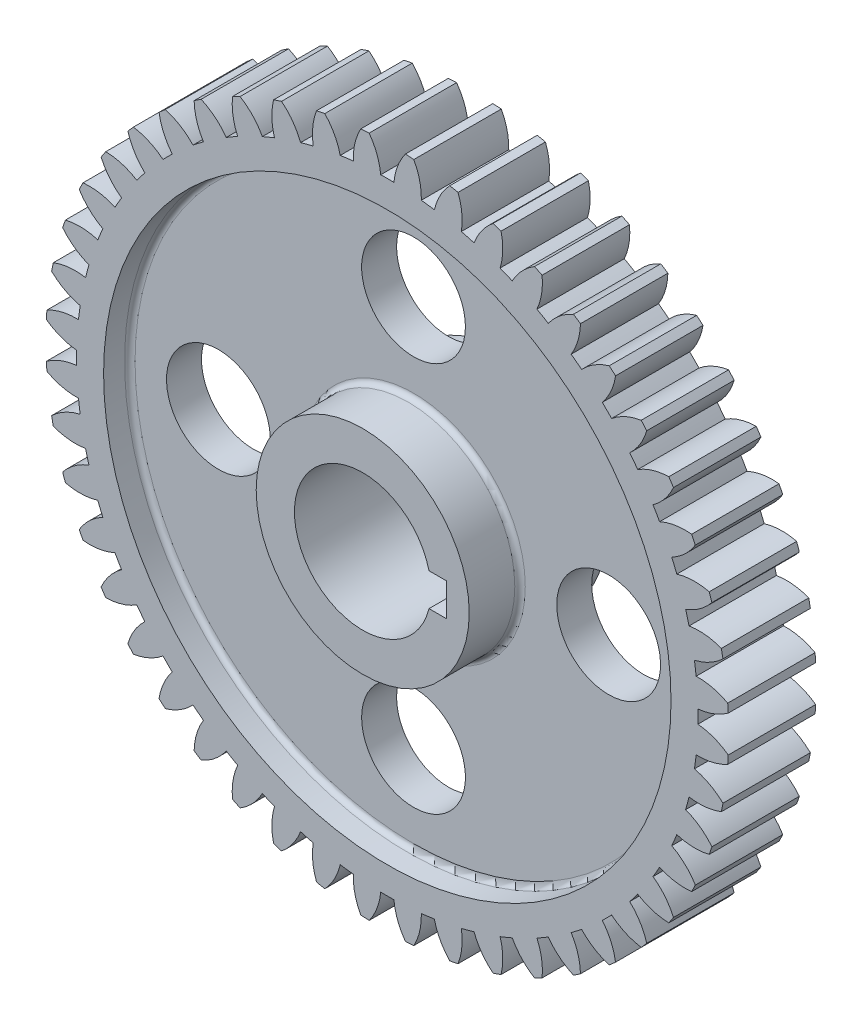
SolidWorks part; units mm, degrees
ref_plane "Front Plane" through (0, 0, 0) normal (0, 0, 1) x (1, 0, 0)
ref_plane "Top Plane" through (0, 0, 0) normal (0, 1, 0) x (1, 0, 0)
ref_plane "Right Plane" through (0, 0, 0) normal (1, 0, 0) x (0, 0, -1)
sketch "HoldingSke" plane through (0, 0, 0) normal (0, 0, 1) x (1, 0, 0)
  line L0 (0, 0) -> (0, -48) construction
  line L1 (0, 0) -> (2.5, 0) construction
  line L2 (0, 0) -> (48, 0) construction
sketch "BasProSke" plane through (0, 0, 0) normal (1, 0, 0) x (0, 0, -1)
  line L0 (-53.9382, 0) -> (60.1411, 0) construction
  line L1 (0, 64.4562) -> (0, -59.6017) construction
  line L3 (-8, 62.5) -> (8, 62.5)
  line L4 (-8, 62.5) -> (-8, 0)
  line L5 (-8, 0) -> (8, 0)
  line L6 (8, 62.5) -> (8, 0)
revolve "Base-Revolve" add sketch "BasProSke" angle 360 about L0
sketch "ToothCutSke" plane through (0, 0, 0) normal (0, 0, 1) x (1, 0, 0)
  line L0 (0, 0) -> (0, 94.1456) construction
  line L1 (0, 0) -> (-5.9046, 90.0862) construction
  line L2 (0, 0) -> (-2.3315, 71.2185) construction
  line L3 (-1.0192, 57.6168) -> (-2.6775, 61.7472) construction
  circle A0 centre (0, 0) radius 56.875 construction
  circle A1 centre (0, 0) radius 62.5 construction
  circle A2 centre (0, 0) radius 60 construction
  arc A3 (-1.2057, 56.8622) -> (-3.3184, 62.4118) centre (-12.4031, 55.7763) ccw
  arc A4 (3.3184, 62.4118) -> (1.2057, 56.8622) centre (12.4031, 55.7763) ccw
  circle A5 centre (0, 0) radius 62.5 construction
  circle A6 centre (0, 0) radius 57.1387 construction
  arc A7 (-3.3184, 62.4118) -> (3.3184, 62.4118) centre (0, 0) cw
  arc A8 (-1.2057, 56.8622) -> (1.2057, 56.8622) centre (0, 0) cw
  point P8 (-1.9631, 59.9679)
  dimension "D4" = 11.25
  dimension "D3" = 1.875
  dimension "D1" = 20
extrude "ToothCut" cut sketch "ToothCutSke" against normal mid plane 16
pattern_circular "TeethCuts" count 49 every 7.5 about axis through (0, 0, 53.9382) along (0, 0, -1) of "ToothCut"
sketch "BSke" plane through (0, 0, 0) normal (0, 0, 1) x (1, 0, 0)
  circle A0 centre (0, 0) radius 19.5
  circle A1 centre (0, 0) radius 12.5 construction
  dimension "Bore_diameter" = 25
extrude "B" [suppressed] add sketch "BSke" along normal blind 25 from surface starting at face at (0, 0, -8)
sketch "CSke" plane through (0, 0, 0) normal (0, 0, 1) x (1, 0, 0)
  circle A0 centre (0, 0) radius 19.5
  circle A1 centre (0, 0) radius 19.5 construction
extrude "C" add sketch "CSke" along normal mid plane 25
sketch "BoreSke" plane through (0, 0, 0) normal (0, 0, 1) x (1, 0, 0)
  circle A0 centre (0, 0) radius 12.5
  dimension "Bore_diameter" = 25
extrude "Bore" cut sketch "BoreSke" against normal mid plane 80
sketch "KeySke" plane through (0, 0, 0) normal (0, 0, 1) x (1, 0, 0)
  line L0 (0, 0) -> (50.2431, 0) construction
  line L1 (15.3, 3) -> (0, 3)
  line L2 (15.3, 3) -> (15.3, -3)
  line L3 (15.3, -3) -> (0, -3)
  line L4 (0, 3) -> (0, -3)
  line L5 (12.5, 26.1066) -> (12.5, -22.6354) construction
  circle A1 centre (0, 0) radius 12.5 construction
  dimension "Keyslot_width" = 6
  dimension "Keyslot_height" = 2.8
extrude "Keyway" cut sketch "KeySke" against normal mid plane 80
sketch "Cut1Ske" plane through (0, 0, 0) normal (1, 0, 0) x (0, 0, -1)
  line L1 (-67.2, 51.9375) -> (-4.16, 51.9375)
  line L2 (-67.2, 51.9375) -> (-67.2, 19.5)
  line L3 (-67.2, 19.5) -> (-4.16, 19.5)
  line L4 (-3.2, 50.9775) -> (-3.2, 20.46)
  line L6 (0, 100.416) -> (0, -72.3489) construction
  line L7 (-40.3305, 0) -> (50.0139, 0) construction
  line L8 (67.2, 19.5) -> (4.16, 19.5)
  line L9 (3.2, 50.9775) -> (3.2, 20.46)
  line L10 (67.2, 51.9375) -> (4.16, 51.9375)
  line L11 (67.2, 51.9375) -> (67.2, 19.5)
  arc A0 (-4.16, 51.9375) -> (-3.2, 50.9775) centre (-4.16, 50.9775) cw
  arc A1 (-4.16, 19.5) -> (-3.2, 20.46) centre (-4.16, 20.46) ccw
  arc A2 (4.16, 19.5) -> (3.2, 20.46) centre (4.16, 20.46) cw
  arc A3 (4.16, 51.9375) -> (3.2, 50.9775) centre (4.16, 50.9775) ccw
  dimension "D3" = 0.96
  dimension "D1" = 39
  dimension "D2" = 64
revolve "Cut1" cut sketch "Cut1Ske" angle 360 about L7
sketch "Cut2Ske" plane through (0, 0, 0) normal (0, 0, 1) x (1, 0, 0)
  line L0 (0, 0) -> (0, 66.9504) construction
  circle A0 centre (0, 0) radius 35.7188 construction
  circle A1 centre (0, 35.7188) radius 9.5
extrude "Cut2" cut sketch "Cut2Ske" against normal mid plane 16
pattern_circular "CirPattern2" count 4 over 360 about axis through (0, 0, 53.9382) along (0, 0, -1) of "Cut2"
equation "\"Ang@ToothCutSke\" = 360/\"Teeth_Num@HoldingSke\"/2"
equation "\"Diameter_O@ToothCutSke\" = \"Teeth_Num@HoldingSke\" * \"Module_value@HoldingSke\""
equation "\"D3@ToothCutSke\" = \"Ang@ToothCutSke\" / 2"
equation "\"D4@ToothCutSke\" =  ( \"Diameter_K@BasProSke\"  - \"Diameter_R@ToothCutSke\") "
equation "\"D2@TeethCuts\" = \"Ang@ToothCutSke\" * 2"
equation "\"ShowTeech_Num@TeethCuts\" = \"ShowTeech_Num@HoldingSke\" + 1"
equation "\"D1@ToothCut\" = \"Face_thickness@BasProSke\""
equation "\"Bore_diameter@BoreSke\" = \"Bore_diameter@BSke\""
equation "\"Diameter_H@BSke\" =  int( \"Bore_diameter@BSke\" * 1.5+1.5  ) "
equation "\"D1@C\" = \"Thickness@B\""
equation "\"D1@Bore\" = \"Face_thickness@BasProSke\"*5"
equation "\"D1@Keyway\" = \"D1@Bore\""
equation "\"D1@Cut1Ske\" = \"Diameter_H@BSke\""
equation "\"D2@Cut1Ske\" = \"Cut_thickness@Cut1Ske\"*10"
equation "\"D3@Cut1Ske\" = \"Cut_thickness@Cut1Ske\"*0.15"
equation "\"Diameter_i@Cut1Ske\" = \"Diameter_R@ToothCutSke\"*0.9+1.5"
equation "\"Cut_thickness@Cut1Ske\" = \"Face_thickness@BasProSke\"*0.4"
equation "\"D1@Cut2\" = \"Face_thickness@BasProSke\""
equation "\"Diameter_C@Cut2Ske\" =  ( \"Diameter_H@BSke\" + \"Diameter_i@Cut1Ske\" )  / 2"
equation "\"Diameter_p@Cut2Ske\" = 1 +  int( ( \"Diameter_i@Cut1Ske\" - \"Diameter_H@BSke\" )  / 3.5 ) "
